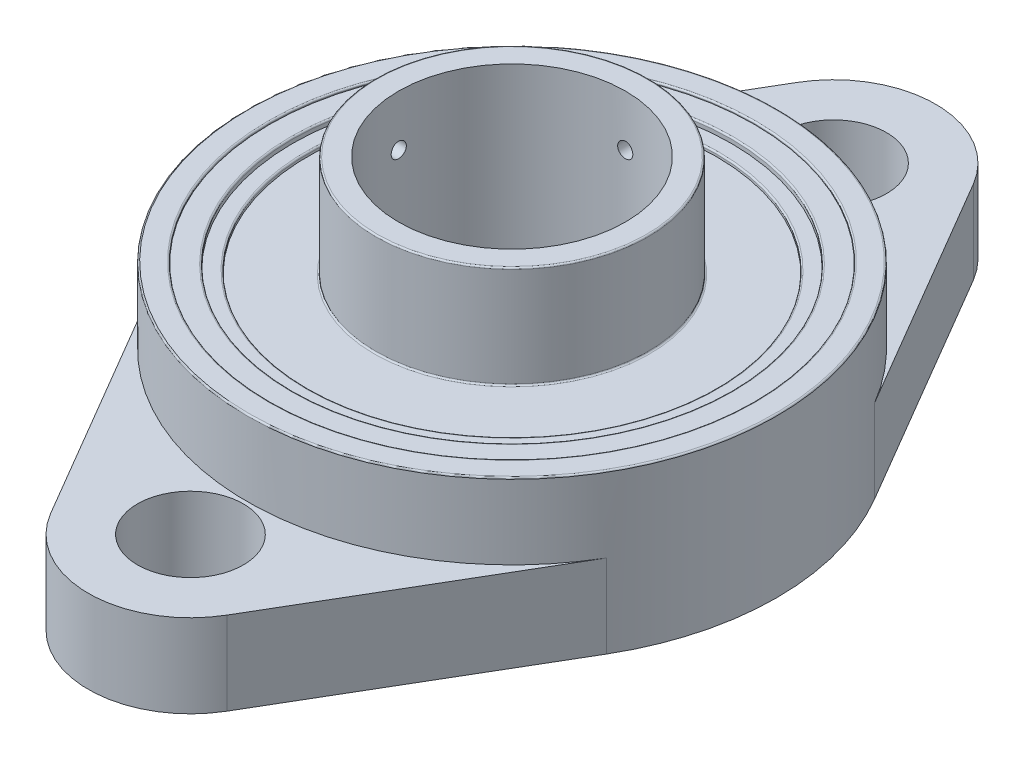
SolidWorks part; units mm, degrees
ref_plane "Front Plane" through (0, 0, 0) normal (0, 0, 1) x (1, 0, 0)
ref_plane "Top Plane" through (0, 0, 0) normal (0, 1, 0) x (1, 0, 0)
ref_plane "Right Plane" through (0, 0, 0) normal (1, 0, 0) x (0, 0, -1)
sketch "Sketch1" plane through (0, 0, 0) normal (0, 1, 0) x (1, 0, 0)
  line L0 (0, -56) -> (0, 56) construction
  line L1 (0, 0) -> (-50000, 0) construction
  line L2 (30.1911, -17.7059) -> (11.6451, -49.3294)
  line L3 (30.1911, 17.7059) -> (11.6451, 49.3294)
  line L4 (-30.1911, -17.7059) -> (-11.6451, -49.3294)
  line L5 (-30.1911, 17.7059) -> (-11.6451, 49.3294)
  circle A0 centre (0, 0) radius 35
  circle A1 centre (0, 0) radius 15
  circle A2 centre (0, 42.5) radius 7
  circle A3 centre (0, 0) radius 32
  circle A4 centre (0, 0) radius 18
  arc A5 (11.6451, 49.3294) -> (-11.6451, 49.3294) centre (0, 42.5) ccw
  circle A6 centre (0, -42.5) radius 7
  arc A7 (-11.6451, -49.3294) -> (11.6451, -49.3294) centre (0, -42.5) ccw
  circle A8 centre (0, 0) radius 29
  circle A9 centre (0, 0) radius 27
  point P6 (0, 0)
  dimension "D1" = 30
  dimension "D2" = 70
  dimension "D5" = 14
  dimension "D3" = 112
  dimension "D4" = 85
  dimension "D6" = 3
  dimension "D7" = 3
  dimension "D8" = 3
  dimension "D9" = 2
extrude "A1" add sketch "Sketch1" along normal blind 11 contours L4 A7 L2 A0 A6 | A0 A3 | L3 A5 L5 A0 A2 region at (20.3013, 0, 33.1559) region at (0, 0, 34.0101) region at (-20.3013, 0, -33.1559)
extrude "A" add sketch "Sketch1<3>" along normal blind 21 contours A0 A3 region at (0, 0, 34.0101)
sketch "Sketch1<3>" plane through (0, 0, 0) normal (0, 1, 0) x (1, 0, 0) same geometry as "Sketch1"
extrude "A0" add sketch "Sketch1<4>" along normal blind 33 contours A4 A1 region at (-17.4909, 0, 0)
sketch "Sketch1<4>" plane through (0, 0, 0) normal (0, 1, 0) x (1, 0, 0) same geometry as "Sketch1"
extrude "Bearing outer d" add sketch "Sketch1<7>" along normal blind 18 from offset 2 separate body contours A8 A9 region at (-28.1798, 0, 0)
sketch "Sketch1<7>" plane through (0, 0, 0) normal (0, 1, 0) x (1, 0, 0) same geometry as "Sketch1"
extrude "Boss-Extrude6" add sketch "Sketch1<8>" along normal blind 19.5 from offset 1.2 contours A3 A8 region at (-31.0949, 0, 0)
sketch "Sketch1<8>" plane through (0, 0, 0) normal (0, 1, 0) x (1, 0, 0) same geometry as "Sketch1"
extrude "Boss-Extrude7" add sketch "Sketch1<9>" along normal blind 18 from offset 1.5 contours A9 A4 region at (-26.2363, 0, 0)
sketch "Sketch1<9>" plane through (0, 0, 0) normal (0, 1, 0) x (1, 0, 0) same geometry as "Sketch1"
sketch "Sketch2" plane through (0, 0, 0) normal (1, 0, 0) x (0, 0, -1)
  line L0 (0, 0) -> (0, 50000) construction
  line L1 (-17.7059, 0) -> (17.7059, 0) construction
  line L2 (18, 26.25) -> (-18, 26.25) construction
  line L3 (18, 19.5) -> (18, 33) construction
  line L4 (-18, 33) -> (-18, 19.5) construction
  circle A0 centre (0, 26.25) radius 1
  point P4 (0, 0)
  dimension "D1" = 2
extrude "Cut-Extrude1" cut sketch "Sketch2" against normal up to next
sketch "Sketch3" plane through (0, 0, 0) normal (0, 0, 1) x (1, 0, 0)
  line L0 (0, 0) -> (0, 50000) construction
  line L1 (6, 26.25) -> (-49994, 26.25) construction
  line L3 (18, 19.5) -> (18, 33) construction
  circle A0 centre (0, 26.25) radius 1
  point P7 (18, 26.25)
  dimension "D1" = 2
extrude "Cut-Extrude2" cut sketch "Sketch3" against normal up to next
fillet "Fillet1" radius 0.2 1 edges at (0, 20, 27)
fillet "Fillet2" radius 0.2 5 edges at (0, 33, 18) (0, 19.5, 18) (0, 21, 35) (0, 21, 32) (0, 20.7, 29)
equation "\"A\"= \"D1@A\""
equation "\"A0\"= \"D1@A0\""
equation "\"A1\"= \"D1@A1\""
equation "\"D1@Bearing outer d\"=\"D1@Boss-Extrude6\" - 1.5"
equation "\"D1@Boss-Extrude6\"=\"D1@A\" - 1.5"
equation "\"D1@Boss-Extrude7\"= \"D1@Bearing outer d\""
equation "\"S\"= \"D19@Boss-Extrude7\""
equation "\"D19@Boss-Extrude6\"=\"D19@Boss-Extrude7\" - 0.3"
equation "\"H\"= \"D3@Sketch1\""
equation "\"J\"= \"D4@Sketch1\""
equation "\"L\"= \"D2@Sketch1\""
equation "\"N\"= \"D5@Sketch1\""
equation "\"d\"= \"D1@Sketch1\""
